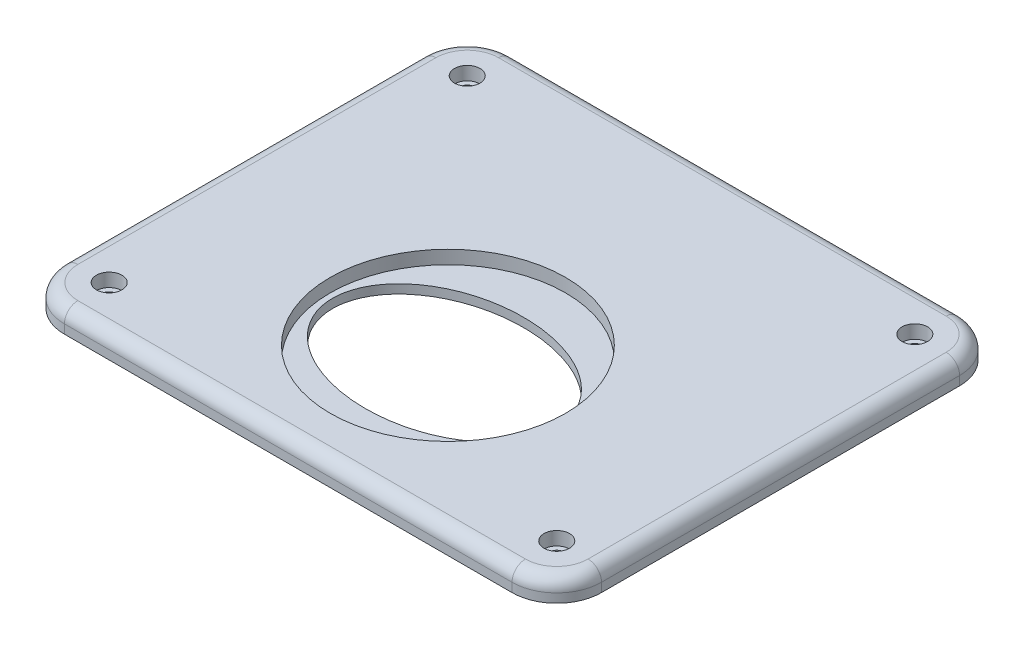
SolidWorks part; units mm, degrees
ref_plane "Front Plane" through (0, 0, 0) normal (0, 0, 1) x (1, 0, 0)
ref_plane "Top Plane" through (0, 0, 0) normal (0, 1, 0) x (1, 0, 0)
ref_plane "Right Plane" through (0, 0, 0) normal (1, 0, 0) x (0, 0, -1)
sketch "Sketch1" plane through (0, 50, 0) normal (0, 1, 0) x (1, 0, 0)
  line L4 (-50, -35.6777) -> (50, -35.6777)
  line L5 (60, -25.6777) -> (60, 54.3223)
  line L6 (50, 64.3223) -> (-50, 64.3223)
  line L7 (-60, 54.3223) -> (-60, -25.6777)
  line L8 (-50, -35.6777) -> (50, -35.6777)
  line L9 (60, -25.6777) -> (60, 54.3223)
  line L10 (50, 64.3223) -> (-50, 64.3223)
  line L11 (-60, 54.3223) -> (-60, -25.6777)
  circle A1 centre (-50, -25.6777) radius 1.7 construction
  circle A2 centre (50, -25.6777) radius 1.7 construction
  circle A3 centre (50, 54.3223) radius 1.7 construction
  circle A4 centre (-50, 54.3223) radius 1.7 construction
  circle A5 centre (-50, -25.6777) radius 1.7
  circle A6 centre (50, -25.6777) radius 1.7
  circle A7 centre (50, 54.3223) radius 1.7
  circle A8 centre (-50, 54.3223) radius 1.7
  circle A9 centre (-50, 54.3223) radius 2.85
  circle A10 centre (-50, -25.6777) radius 2.85
  circle A11 centre (50, 54.3223) radius 2.85
  circle A12 centre (50, -25.6777) radius 2.85
  arc A21 (-50, 64.3223) -> (-60, 54.3223) centre (-50, 54.3223) ccw
  arc A22 (-50, 64.3223) -> (-60, 54.3223) centre (-50, 54.3223) ccw
  arc A23 (-60, -25.6777) -> (-50, -35.6777) centre (-50, -25.6777) ccw
  arc A24 (-60, -25.6777) -> (-50, -35.6777) centre (-50, -25.6777) ccw
  arc A25 (50, -35.6777) -> (60, -25.6777) centre (50, -25.6777) ccw
  arc A26 (50, -35.6777) -> (60, -25.6777) centre (50, -25.6777) ccw
  arc A27 (60, 54.3223) -> (50, 64.3223) centre (50, 54.3223) ccw
  arc A28 (60, 54.3223) -> (50, 64.3223) centre (50, 54.3223) ccw
  circle A283 centre (0, 0) radius 26.3
  circle A284 centre (0, 0) radius 26.3
  ellipse E1 centre (0, -0.7778) end of major axis (-25, -0.7778) minor radius 17.6777
  ellipse E2 centre (0, -0.7778) end of major axis (-25, -0.7778) minor radius 17.6777
  point P32 (0, -0.7778)
  dimension "D4" = 5.7
  dimension "D5" = 5.7
  dimension "D6" = 5.7
  dimension "D7" = 5.7
  dimension "D1" = 0
  dimension "D2" = 0
  dimension "D3" = 0.3
extrude "Boss-Extrude1" add sketch "Sketch1" along normal blind 2 contours E2 | L9 A28 L10 A22 L11 A24 L8 A26 | A8 | A7 | A6 | A5 region at (0, 50, 0.7778)
extrude "Boss-Extrude2" add sketch "Sketch1<3>" along normal blind 3 from surface contours L10 A22 L11 A24 L8 A26 L9 A28 | A9 | A11 | A12 | A10 | A284 starting at face at (50, 52, 27.3777)
sketch "Sketch1<3>" plane through (0, 50, 0) normal (0, 1, 0) x (1, 0, 0) same geometry as "Sketch1"
fillet "Fillet1" radius 3 8 edges at (-57.0711, 55, -61.3934) (-60, 55, -14.3223) (-57.0711, 55, 32.7487) (0, 55, 35.6777) (57.0711, 55, 32.7487) (60, 55, -14.3223) (57.0711, 55, -61.3934) (0, 55, -64.3223)
equation "\"D5@Sketch1\"=\"D4@Sketch1\""
equation "\"D6@Sketch1\"=\"D4@Sketch1\""
equation "\"D7@Sketch1\"=\"D4@Sketch1\""
